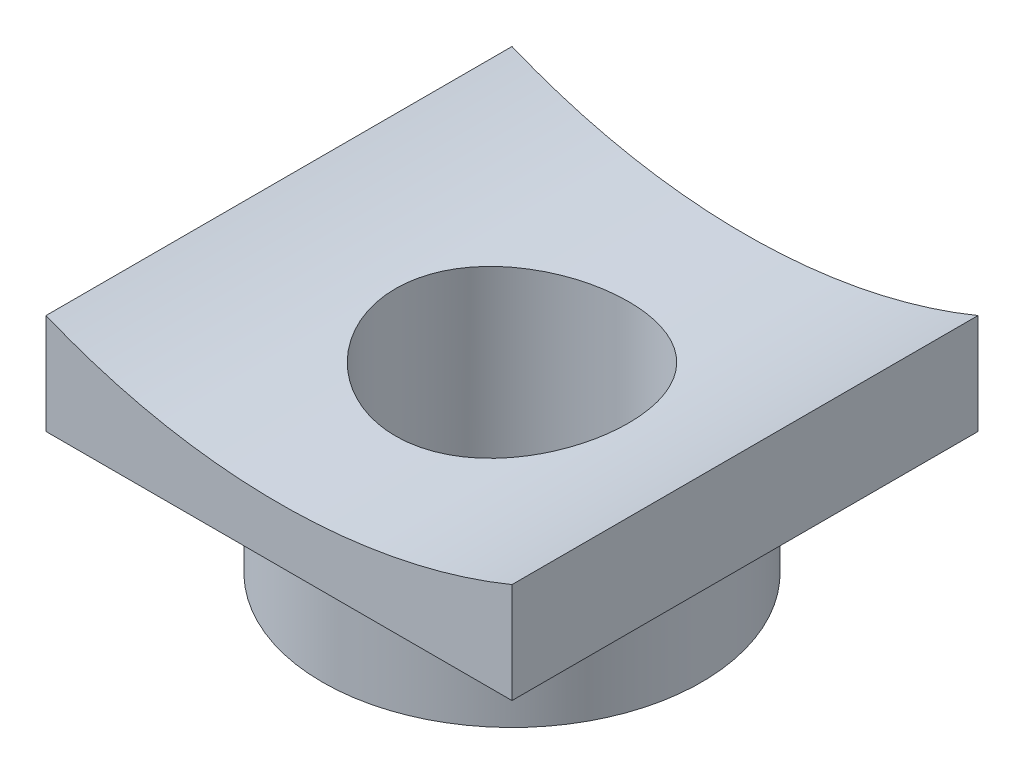
SolidWorks part; units mm, degrees
ref_plane "Plano frontal" through (0, 0, 0) normal (0, 0, 1) x (1, 0, 0)
ref_plane "Plano superior" through (0, 0, 0) normal (0, 1, 0) x (1, 0, 0)
ref_plane "Plano direito" through (0, 0, 0) normal (1, 0, 0) x (0, 0, -1)
ref_plane "Plano1" through (0, 0, -38.1) normal (0, 0, -1) x (-1, 0, 0)
sketch "Esboço1" plane through (0, 0, -38.1) normal (0, 0, -1) x (-1, 0, 0)
  line L0 (-38.1, -3.5741) -> (-38.1, -20)
  line L1 (-38.1, -20) -> (38.1, -20)
  line L2 (38.1, -20) -> (38.1, -3.5741)
  arc A0 (38.1, -3.5741) -> (-38.1, -3.5741) centre (0, 88.8834) cw
extrude "Ressalto-extrusão1" add sketch "Esboço1" against normal blind 76.2
ref_plane "Plano2" through (0, 0, 0) normal (0, 0, -1) x (-1, 0, 0)
sketch "Esboço2" plane through (0, 0, 0) normal (0, 0, -1) x (-1, 0, 0)
  line L0 (-31, -40) -> (0, -40)
  line L1 (0, -40) -> (0, -20)
  line L2 (0, -20) -> (-31, -20)
  line L3 (-31, -20) -> (-31, -40)
  line L4 (0, -40) -> (0, -20) construction
revolve "Revolução1" add sketch "Esboço2" angle 360 about L4 reverse direction yes
hole_wizard "Furo com folga de M361" positions "Esboço4" profile "Esboço3" hole size "M36" standard "Ansi Metric"
sketch "Esboço4" plane through (0, -40, 0) normal (0, -1, 0) x (-1, 0, 0)
  point P0 (0, 0)
sketch "Esboço3" plane through (0, -40, 0) normal (1, 0, 0) x (0, 0, -1)
  line L0 (0, 0) -> (0, 36.4259)
  line L1 (0, 36.4259) -> (19.05, 36.4259)
  line L2 (19.05, 36.4259) -> (19.05, 0)
  line L5 (19.05, 0) -> (0, 0)
  line L11 (0, -6.35) -> (0, 107.95) construction
  dimension "Thru Hole Dia." = 38.1
  dimension "Thru Hole Depth" = 36.4259
